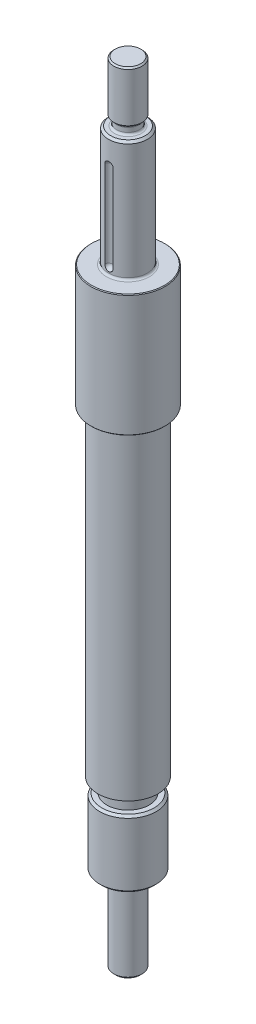
SolidWorks part; units mm, degrees
ref_plane "Front Plane" through (0, 0, 0) normal (0, 0, 1) x (1, 0, 0)
ref_plane "Top Plane" through (0, 0, 0) normal (0, 1, 0) x (1, 0, 0)
ref_plane "Right Plane" through (0, 0, 0) normal (1, 0, 0) x (0, 0, -1)
sketch "Sketch1" plane through (0, 0, 0) normal (0, 0, 1) x (1, 0, 0)
  line L0 (0, 0) -> (0, 119.1505) construction
  line L1 (0, 0) -> (2, 0)
  line L2 (2, 0) -> (2, 12)
  line L3 (2, 12) -> (4, 12)
  line L4 (4, 12) -> (4, 21.5)
  line L5 (4.25, 69) -> (5.25, 69)
  line L7 (5.25, 86.3) -> (2.75, 86.3)
  line L8 (2.75, 86.3) -> (2.75, 103.3)
  line L9 (2, 111.8) -> (0, 111.8)
  line L10 (2, 111.8) -> (2, 104.5)
  line L11 (1.6, 103.3) -> (2.75, 103.3)
  line L12 (0, 111.8) -> (0, 0)
  line L13 (5.25, 86.3) -> (5.25, 69)
  line L15 (2, 104.5) -> (1.6, 104.5)
  line L16 (1.6, 104.5) -> (1.6, 103.3)
  line L17 (4.25, 23.5) -> (4.25, 69)
  line L18 (4, 21.5) -> (3, 21.5)
  line L20 (4.25, 23.5) -> (3, 23.5)
  line L21 (3, 21.5) -> (3, 23.5)
  line L22 (0, 0) -> (0, -13.7807) construction
  dimension "D1" = 17.3
  dimension "D2" = 8
  dimension "D3" = 5.5
  dimension "D4" = 4
  dimension "D5" = 3.2
  dimension "D6" = 17
  dimension "D7" = 10.5
  dimension "D8" = 1.2
  dimension "D9" = 25.5
  dimension "D10" = 45.5
  dimension "D11" = 12
  dimension "D12" = 6
  dimension "D13" = 2
  dimension "D14" = 11.5
  dimension "D15" = 8.5
revolve "Revolve1" add sketch "Sketch1" angle 360 about L0
ref_plane "Plane2" through (0, 86.8, 0) normal (0, 1, 0) x (1, 0, 0)
sketch "Sketch2" plane through (0, 86.8, 0) normal (0, 1, 0) x (1, 0, 0)
  line L0 (0, 0) -> (6.8447, 0) construction
  circle A0 centre (0, 2.75) radius 0.6
  circle A1 centre (0, 0) radius 2.75 construction
  circle A2 centre (0, 0) radius 2.75 construction
  circle A3 centre (0, -2.75) radius 0.6
  dimension "D1" = 1.2
extrude "Cut-Extrude1" cut sketch "Sketch2" along normal offset from surface (13.5 mm away) 3 up to face at (0, 103.3, -1.6)
fillet "Fillet1" radius 0.6 4 edges at (0, 100.3, -2.15) (0, 86.8, -2.15) (0, 86.8, 2.15) (0, 100.3, 2.15)
chamfer "Chamfer1" distance 0.1 angle 45 2 edges at (0, 69, -5.25) (0, 86.3, -5.25)
chamfer "Chamfer2" distance 0.3 angle 45 2 edges at (0, 21.5, -4) (0, 12, -4)
chamfer "Chamfer3" distance 0.3 angle 45 1 edges at (0, 0, -2)
chamfer "Chamfer4" distance 0.3 angle 45 1 edges at (0, 103.3, -2.75)
chamfer "Chamfer5" distance 0.2 angle 45 2 edges at (0, 104.5, -2) (0, 111.8, -2)
fillet "Fillet2" radius 0.3 6 edges at (0, 23.5, -3) (0, 12, -2) (0, 69, -4.25) (0, 86.3, -2.75) (0, 104.5, -1.6) (0, 103.3, -1.6)
